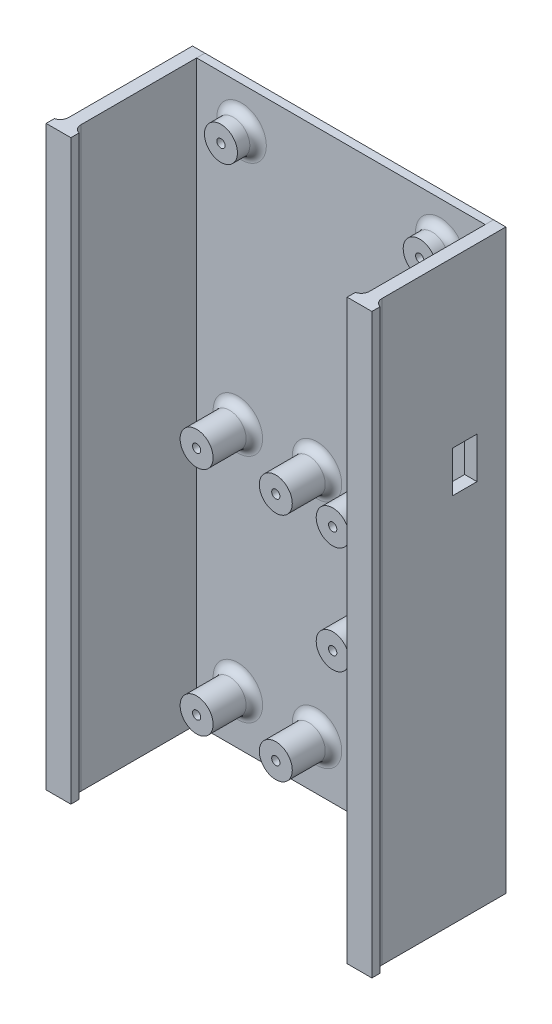
SolidWorks part; units mm, degrees
ref_plane "Přední rovina" through (0, 0, 0) normal (0, 0, 1) x (1, 0, 0)
ref_plane "Horní rovina" through (0, 0, 0) normal (0, 1, 0) x (1, 0, 0)
ref_plane "Pravá rovina" through (0, 0, 0) normal (1, 0, 0) x (0, 0, -1)
sketch "Skica1" plane through (0, 0, 0) normal (0, 0, 1) x (1, 0, 0)
  line L1 (0, 0) -> (70, 0)
  line L2 (0, 0) -> (0, 140)
  line L3 (0, 140) -> (70, 140)
  line L4 (70, 0) -> (70, 140)
  dimension "D1" = 140
  dimension "D2" = 70
extrude "Přidat vysunutím1" add sketch "Skica1" along normal blind 2
sketch "Skica2" plane through (0, 0, 2) normal (0, 0, 1) x (1, 0, 0)
  line L1 (70, 140) -> (0, 140) construction
  line L5 (0, 140) -> (0, 0) construction
  line L9 (70, 0) -> (70, 140) construction
  line L10 (0, 0) -> (70, 0) construction
  circle A0 centre (59.1, 130) radius 1
  circle A1 centre (10.9, 130) radius 1
  circle A2 centre (10, 68) radius 1
  circle A3 centre (29.2, 68) radius 1
  circle A4 centre (10, 12) radius 1
  circle A5 centre (29.2, 12) radius 1
  circle A6 centre (43, 68) radius 1
  circle A7 centre (60, 68) radius 1
  circle A8 centre (60, 42) radius 1
  circle A9 centre (55, 30) radius 1
  circle A10 centre (10, 68) radius 4
  circle A11 centre (29.2, 68) radius 4
  circle A12 centre (43, 68) radius 4
  circle A13 centre (60, 68) radius 4
  circle A14 centre (60, 42) radius 4
  circle A15 centre (55, 30) radius 4
  circle A16 centre (29.2, 12) radius 4
  circle A17 centre (10, 12) radius 4
  circle A18 centre (10.9, 130) radius 4
  circle A19 centre (59.1, 130) radius 4
  circle A20 centre (43, 42) radius 1
  circle A21 centre (43, 42) radius 4
  dimension "D1" = 2
  dimension "D2" = 2
  dimension "D3" = 48.2
  dimension "D5" = 10.9
  dimension "D6" = 10
  dimension "D7" = 2
  dimension "D8" = 2
  dimension "D9" = 2
  dimension "D10" = 2
  dimension "D11" = 2
  dimension "D12" = 2
  dimension "D13" = 2
  dimension "D14" = 56
  dimension "D15" = 56
  dimension "D16" = 10
  dimension "D17" = 62
  dimension "D18" = 19.2
  dimension "D19" = 19.2
  dimension "D20" = 10
  dimension "D21" = 12
  dimension "D22" = 26
  dimension "D23" = 0
  dimension "D24" = 17
  dimension "D25" = 10
  dimension "D26" = 62
  dimension "D27" = 42
  dimension "D28" = 30
  dimension "D29" = 2
  dimension "D30" = 15
  dimension "D31" = 8
  dimension "D32" = 8
  dimension "D33" = 8
  dimension "D34" = 8
  dimension "D35" = 8
  dimension "D36" = 8
  dimension "D37" = 8
  dimension "D38" = 8
  dimension "D39" = 8
  dimension "D40" = 8
  dimension "D42" = 2
  dimension "D43" = 8
  dimension "D44" = 17
  dimension "D45" = 26
  dimension "D41" = 62
extrude "Přidat vysunutím2" add sketch "Skica2" along normal blind 10
sketch "Skica4" plane through (0, 0, 0) normal (0, 0, 1) x (1, 0, 0)
  line L1 (0, 0) -> (-3, 0)
  line L2 (0, 0) -> (0, 140)
  line L3 (0, 140) -> (-3, 140)
  line L4 (-3, 0) -> (-3, 140)
  line L25 (35, 128.5362) -> (35, -20.7413) construction
  line L34 (73, 0) -> (73, 140)
  line L52 (70, 140) -> (73, 140)
  line L53 (70, 0) -> (70, 140)
  line L54 (70, 0) -> (73, 0)
  dimension "D4" = 140
  dimension "D12" = 35
  dimension "D14" = 3
extrude "Přidat vysunutím3" add sketch "Skica4" along normal blind 32 separate body contours L4 L1 L3 | L52 L54 region at (-1.5, 70, 0) region at (71.5, 70, 0)
sketch "Skica5" plane through (73, 0, 0) normal (1, 0, 0) x (0, 0, -1)
  line L0 (0, 0) -> (0, 140) construction
  line L1 (-13, 90) -> (-7, 90)
  line L2 (-13, 90) -> (-13, 100)
  line L3 (-13, 100) -> (-7, 100)
  line L4 (-7, 90) -> (-7, 100)
  line L5 (-13, 100) -> (-7, 100)
  line L6 (0, 140) -> (-32, 140) construction
  dimension "D1" = 40
  dimension "D2" = 10
  dimension "D3" = 6
  dimension "D4" = 7
extrude "Odebrat vysunutím2" cut sketch "Skica5" against normal blind 20 contours L3 L4 L1 L2
sketch "Skica6" plane through (0, 0, 12) normal (0, 0, 1) x (1, 0, 0)
  circle A0 centre (10.9, 130) radius 4
  circle A1 centre (59.1, 130) radius 4
  dimension "D1" = 8
  dimension "D2" = 8
extrude "Odebrat vysunutím3" cut sketch "Skica6" against normal blind 5
fillet "Zaoblit1" radius 2 11 edges at (6, 12, 2) (25.2, 12, 2) (51, 30, 2) (56, 42, 2) (6.9, 130, 2) (55.1, 130, 2) (56, 68, 2) (39, 68, 2) (25.2, 68, 2) (6, 68, 2) (39, 42, 2)
sketch "Skica7" plane through (0, 0, 0) normal (0, -1, 0) x (1, 0, 0)
  line L0 (0, 32) -> (0, 0) construction
  line L1 (1.5, 32) -> (-4.5, 32)
  line L2 (1.5, 32) -> (1.5, 34)
  line L3 (1.5, 34) -> (-4.5, 34)
  line L4 (-4.5, 32) -> (-4.5, 34)
  line L10 (35, 57.629) -> (35, -12.1968) construction
  line L11 (74.5, 32) -> (74.5, 34)
  line L12 (68.5, 34) -> (74.5, 34)
  line L13 (68.5, 32) -> (68.5, 34)
  line L14 (68.5, 32) -> (74.5, 32)
  line L15 (0, 0) -> (-3, 0) construction
  dimension "D1" = 1.5
  dimension "D2" = 32
  dimension "D3" = 2
  dimension "D4" = 6
  dimension "D5" = 35
extrude "Přidat vysunutím4" add sketch "Skica7" against normal blind 140
fillet "Zaoblit2" radius 2 2 edges at (-3, 70, 32) (0, 70, 32)
fillet "Zaoblit3" radius 2 2 edges at (73, 70, 32) (70, 70, 32)
